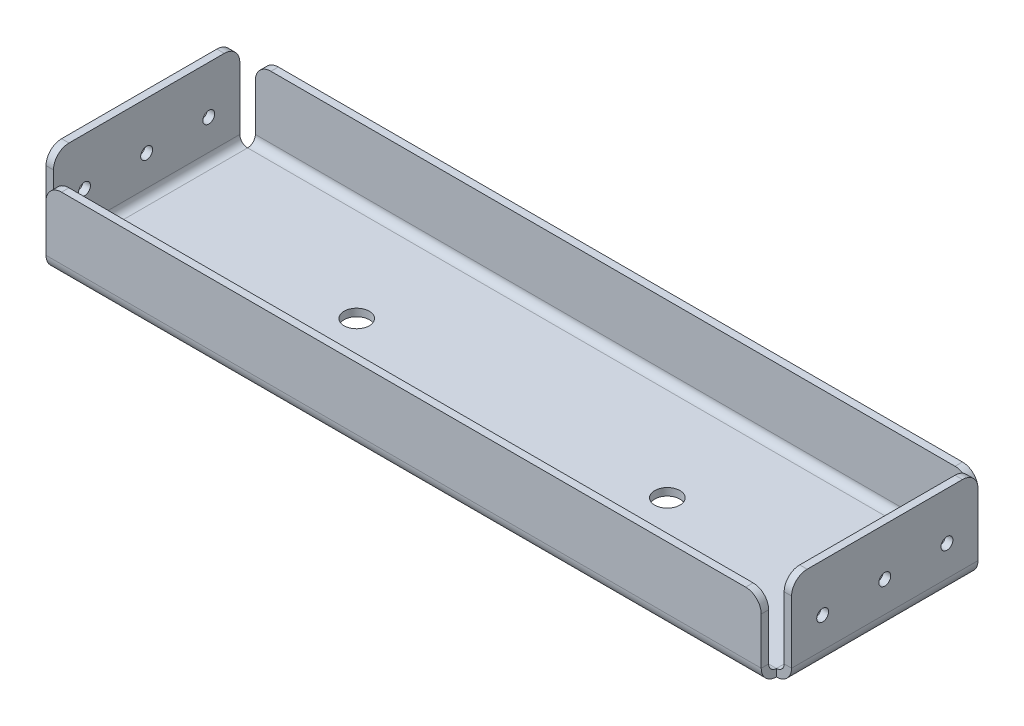
SolidWorks part; units mm, degrees
note: The reader was unsure of these and kept them because the rebuilt part matched: flange length of "Edge-Flange1", "Edge-Flange2".
ref_plane "Front Plane" through (0, 0, 0) normal (0, 0, 1) x (1, 0, 0)
ref_plane "Top Plane" through (0, 0, 0) normal (0, 1, 0) x (1, 0, 0)
ref_plane "Right Plane" through (0, 0, 0) normal (1, 0, 0) x (0, 0, -1)
sketch "Sketch1" plane through (0, 0, 0) normal (0, 1, 0) x (1, 0, 0)
  line L1 (0, 0) -> (304.8, 0)
  line L2 (0, 0) -> (0, 76.2)
  line L3 (0, 76.2) -> (304.8, 76.2)
  line L4 (304.8, 0) -> (304.8, 76.2)
  dimension "D1" = 304.8
  dimension "D2" = 76.2
base flange "Base-Flange1" sketch "Sketch1" thickness 3.0378 reverse thickness direction no parameters "D1"=3.175
edge flange "Edge-Flange1" sketch "Sketch10" flange profiles "Sketch10", "Sketch11" flange angle 90 flange length 38.1 flange position material inside bend radius 3.175 thickness 3.0378 parameters "D1"=3.81, "D6"=10, "D8"=1
sketch "Sketch10" plane through (0, 0, 0) normal (-1, 0, 0) x (0, 0, 1)
  line L2 (-76.2, 0) -> (-76.2, 35.0622)
  line L3 (-76.2, 35.0622) -> (0, 35.0622)
  line L4 (0, 35.0622) -> (0, 0)
  line L7 (-76.2, 0) -> (0, 0) construction
  line L8 (-76.2, 0) -> (0, 0)
sketch "Sketch11" plane through (304.8, 0, 0) normal (1, 0, 0) x (0, 0, -1)
  line L2 (0, 0) -> (0, 35.0622)
  line L3 (0, 35.0622) -> (76.2, 35.0622)
  line L4 (76.2, 35.0622) -> (76.2, 0)
  line L7 (0, 0) -> (76.2, 0) construction
  line L8 (0, 0) -> (76.2, 0)
bend "EdgeBend1" bend radius 3.175 bend angle 90 parameters "D5"=1
bend "EdgeBend2" bend radius 3.175 bend angle 90 parameters "D5"=2
edge flange "Edge-Flange2" sketch "Sketch16" flange profiles "Sketch16", "Sketch17" flange angle 90 flange length 31.75 flange position bend outside bend radius 3.175 thickness 3.0378 parameters "D1"=3.81, "D6"=10, "D8"=1
sketch "Sketch16" plane through (0, 0, 0) normal (0, 0, 1) x (1, 0, 0)
  line L0 (6.2128, 0) -> (298.5872, 0) construction
  line L1 (6.2128, 0) -> (298.5872, 0)
  line L2 (6.2128, 0) -> (6.2128, 28.7122)
  line L3 (6.2128, 28.7122) -> (298.5872, 28.7122)
  line L4 (298.5872, 28.7122) -> (298.5872, 0)
sketch "Sketch17" plane through (0, 0, -76.2) normal (0, 0, -1) x (-1, 0, 0)
  line L0 (-298.5872, 0) -> (-6.2128, 0) construction
  line L1 (-298.5872, 0) -> (-6.2128, 0)
  line L2 (-298.5872, 0) -> (-298.5872, 28.7122)
  line L3 (-298.5872, 28.7122) -> (-6.2128, 28.7122)
  line L4 (-6.2128, 28.7122) -> (-6.2128, 0)
bend "EdgeBend3" bend radius 3.175 bend angle 90 parameters "D5"=3
bend "EdgeBend4" bend radius 3.175 bend angle 90 parameters "D5"=4
hole_wizard "3/8 Clearance Hole1" positions "Sketch18" profile "Sketch19" hole size "3/8" standard "ANSI Inch" end condition through all
sketch "Sketch18" plane through (0, -3.0378, 0) normal (0, -1, 0) x (-1, 0, 0)
  line L2 (-298.5872, 76.2) -> (-6.2128, 76.2) construction
  line L3 (-152.4, 76.2) -> (-152.4, 0) construction
  line L4 (-6.2128, 0) -> (-298.5872, 0) construction
  line L5 (-6.2128, 0) -> (-6.2128, 76.2) construction
  point P0 (-88.9, 38.1)
  point P2 (-215.9, 38.1)
  point P14 (0, 0)
  dimension "D1" = 63.5
  dimension "D2" = 127
  dimension "D3" = 38.1
  dimension "D4" = 82.6872
sketch "Sketch19" plane through (88.9, -3.0378, -38.1) normal (1, 0, 0) x (0, 0, -1)
  line L0 (0, 0) -> (0, 38.1)
  line L1 (0, 38.1) -> (5.1587, 38.1)
  line L2 (5.1587, 38.1) -> (5.1587, 0)
  line L5 (5.1587, 0) -> (0, 0)
  line L11 (0, -6.35) -> (0, 107.95) construction
  dimension "Thru Hole Dia." = 10.3175
  dimension "Thru Hole Depth" = 38.1
hole_wizard "#11 (0.191) Diameter Hole1" positions "Sketch22" profile "Sketch23" hole size "#11" standard "ANSI Inch" end condition through all
sketch "Sketch22" plane through (304.8, 0, 0) normal (1, 0, 0) x (0, 0, -1)
  line L0 (63.5, 15.6337) -> (12.7, 15.6337) construction
  line L2 (76.2, 35.0622) -> (0, 35.0622) construction
  line L3 (0, 35.0622) -> (0, 3.175) construction
  line L4 (38.1, 35.0622) -> (38.1, 3.175) construction
  line L5 (76.2, 3.175) -> (0, 3.175) construction
  line L8 (76.2, 3.175) -> (76.2, 35.0622) construction
  point P0 (12.7, 15.6337)
  point P2 (38.1, 15.6337)
  point P4 (63.5, 15.6337)
  dimension "D1" = 19.4285
  dimension "D2" = 12.7
  dimension "D3" = 12.7
  dimension "D4" = 25.4
sketch "Sketch23" plane through (304.8, 15.6337, -12.7) normal (0, 1, 0) x (0, 0, -1)
  line L0 (0, 0) -> (0, 304.8)
  line L1 (0, 304.8) -> (2.4257, 304.8)
  line L2 (2.4257, 304.8) -> (2.4257, 0)
  line L5 (2.4257, 0) -> (0, 0)
  line L11 (0, -6.35) -> (0, 107.95) construction
  dimension "Thru Hole Dia." = 4.8514
  dimension "Thru Hole Depth" = 304.8
fillet "Fillet1" radius 6.35
sketch "Bend-Lines1" [suppressed] plane through (0, 0, 0) normal (0, 1, 0) x (1, 0, 0)
sketch "Bounding-Box1" [suppressed] plane through (0, 0, 0) normal (0, 1, 0) x (1, 0, 0)
sheet metal parameters "Sheet-Metal1" thickness 3.0378 parameters "D1"=3.81
flat pattern "Flat-Pattern1" [suppressed]
sketch "Bend-Lines2" plane through (0, 0, 0) normal (0, 1, 0) x (1, 0, 0)
sketch3d "Bounding-Box2" [suppressed]
  line L0 (-304.8, 76.2, 0) -> (0, 76.2, 0) construction
  line L1 (-304.8, 0, 0) -> (0, 0, 0) construction
  line L2 (-304.8, 76.2, 0) -> (-304.8, 0, 0) construction
  line L3 (0, 76.2, 0) -> (0, 0, 0) construction
sheet metal parameters "Sheet-Metal2" thickness 3.0378 parameters "D1"=3.81
flat pattern "Flat-Pattern1"
sketch "Bend-Lines2" plane through (0, 0, 0) normal (0, 1, 0) x (1, 0, 0)
  line L0 (305.3239, 0) -> (305.3239, 76.2) construction
  line L1 (-0.5239, 76.2) -> (-0.5239, 0) construction
  line L2 (305.3239, 0) -> (305.3239, 76.2) construction
  line L3 (-0.5239, 76.2) -> (-0.5239, 0) construction
sketch3d "Bounding-Box2" [suppressed]
  line L0 (340.5316, 76.2, 0) -> (-35.7316, 76.2, 0) construction
  line L1 (340.5316, 0, 0) -> (-35.7316, 0, 0) construction
  line L2 (340.5316, 76.2, 0) -> (340.5316, 0, 0) construction
  line L3 (-35.7316, 76.2, 0) -> (-35.7316, 0, 0) construction
bend of the flat pattern "Flatten-<EdgeBend1>1"
bend of the flat pattern "Flatten-<EdgeBend2>1"
sheet metal parameters "Sheet-Metal3" thickness 3.0378 parameters "D1"=3.81
flat pattern "Flat-Pattern1"
sketch "Bend-Lines2" plane through (0, 0, 0) normal (0, 1, 0) x (1, 0, 0)
  line L0 (301.9076, 0) -> (301.9076, 76.2) construction
  line L1 (2.8924, 76.2) -> (2.8924, 0) construction
  line L2 (301.9076, 0) -> (301.9076, 76.2) construction
  line L3 (2.8924, 76.2) -> (2.8924, 0) construction
  line L4 (297.5737, 80.5339) -> (7.2263, 80.5339) construction
  line L5 (7.2263, -4.3339) -> (297.5737, -4.3339) construction
  line L6 (297.5737, 80.5339) -> (7.2263, 80.5339) construction
  line L7 (7.2263, -4.3339) -> (297.5737, -4.3339) construction
sketch3d "Bounding-Box2" [suppressed]
  line L0 (337.1153, 109.3916, 0) -> (-32.3153, 109.3916, 0) construction
  line L1 (337.1153, -33.1916, 0) -> (-32.3153, -33.1916, 0) construction
  line L2 (337.1153, 109.3916, 0) -> (337.1153, -33.1916, 0) construction
  line L3 (-32.3153, 109.3916, 0) -> (-32.3153, -33.1916, 0) construction
bend of the flat pattern "Flatten-<EdgeBend1>1"
bend of the flat pattern "Flatten-<EdgeBend2>1"
bend of the flat pattern "Flatten-<EdgeBend3>1"
bend of the flat pattern "Flatten-<EdgeBend4>1"
sheet metal parameters "Sheet-Metal4" thickness 3.0378 parameters "D1"=3.81
flat pattern "Flat-Pattern1"
sketch "Bend-Lines2" plane through (0, 0, 0) normal (0, 1, 0) x (1, 0, 0)
  line L0 (301.9076, 0) -> (301.9076, 76.2) construction
  line L1 (2.8924, 76.2) -> (2.8924, 0) construction
  line L2 (301.9076, 0) -> (301.9076, 76.2) construction
  line L3 (2.8924, 76.2) -> (2.8924, 0) construction
  line L4 (297.5737, 80.5339) -> (7.2263, 80.5339) construction
  line L5 (7.2263, -4.3339) -> (297.5737, -4.3339) construction
  line L6 (297.5737, 80.5339) -> (7.2263, 80.5339) construction
  line L7 (7.2263, -4.3339) -> (297.5737, -4.3339) construction
sketch3d "Bounding-Box2" [suppressed]
  line L0 (337.1153, 109.3916, 0) -> (-32.3153, 109.3916, 0) construction
  line L1 (337.1153, -33.1916, 0) -> (-32.3153, -33.1916, 0) construction
  line L2 (337.1153, 109.3916, 0) -> (337.1153, -33.1916, 0) construction
  line L3 (-32.3153, 109.3916, 0) -> (-32.3153, -33.1916, 0) construction
bend of the flat pattern "Flatten-<EdgeBend1>1"
bend of the flat pattern "Flatten-<EdgeBend2>1"
bend of the flat pattern "Flatten-<EdgeBend3>1"
bend of the flat pattern "Flatten-<EdgeBend4>1"
sheet metal parameters "Sheet-Metal5" thickness 3.0378 parameters "D1"=3.81
flat pattern "Flat-Pattern1" [suppressed]
sketch "Bend-Lines2" plane through (0, 0, 0) normal (0, 1, 0) x (1, 0, 0)
  line L0 (302.2738, 0) -> (302.2738, 76.2) construction
  line L1 (2.5262, 76.2) -> (2.5262, 0) construction
  line L2 (302.2738, 0) -> (302.2738, 76.2) construction
  line L3 (2.5262, 76.2) -> (2.5262, 0) construction
  line L4 (298.5872, 79.8866) -> (6.2128, 79.8866) construction
  line L5 (6.2128, -3.6866) -> (298.5872, -3.6866) construction
  line L6 (298.5872, 79.8866) -> (6.2128, 79.8866) construction
  line L7 (6.2128, -3.6866) -> (298.5872, -3.6866) construction
sketch3d "Bounding-Box2" [suppressed]
  line L0 (-33.0475, 109.1103, 0) -> (337.8475, 109.1104, 0) construction
  line L1 (-33.0475, -32.9104, 0) -> (337.8475, -32.9103, 0) construction
  line L2 (-33.0475, 109.1103, 0) -> (-33.0475, -32.9104, 0) construction
  line L3 (337.8475, 109.1104, 0) -> (337.8475, -32.9103, 0) construction
bend of the flat pattern "Flatten-<EdgeBend1>1"
bend of the flat pattern "Flatten-<EdgeBend2>1"
bend of the flat pattern "Flatten-<EdgeBend3>1"
bend of the flat pattern "Flatten-<EdgeBend4>1"
